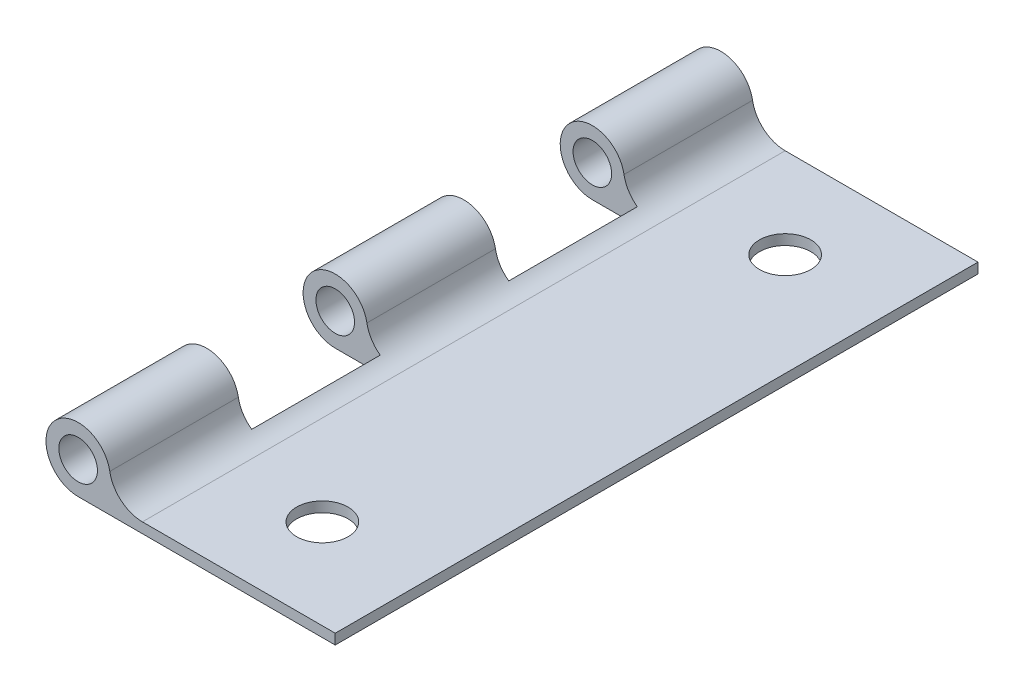
SolidWorks part; units mm, degrees
material "Aço cromo inoxidável"
ref_plane "Plano frontal" through (0, 0, 0) normal (0, 0, 1) x (1, 0, 0)
ref_plane "Plano superior" through (0, 0, 0) normal (0, 1, 0) x (1, 0, 0)
ref_plane "Plano direito" through (0, 0, 0) normal (1, 0, 0) x (0, 0, -1)
sketch "Esboço1" plane through (0, 0, 0) normal (0, 0, 1) x (1, 0, 0)
  line L0 (0, 0) -> (-20, 0)
  line L2 (-15, 0.8) -> (0, 0.8)
  line L3 (0, 0.8) -> (0, 0)
  arc A0 (-20, 0) -> (-19.9579, 4.9996) centre (-20, 2.5) cw
  arc A1 (-19.9579, 4.9996) -> (-17.5375, 2.9315) centre (-20, 2.5) cw
  arc A2 (-17.5375, 2.9315) -> (-15, 0.8) centre (-15, 3.3762) ccw
  circle A3 centre (-20, 2.5) radius 1.5
  circle A4 centre (-20, 2.5) radius 1.5 construction
  dimension "D4" = 20
  dimension "D5" = 1
  dimension "D1" = 0.8
  dimension "D3" = 5
extrude "Ressalto-extrusão1" add sketch "Esboço1" along normal blind 50
sketch "Esboço2" plane through (0, 0, 0) normal (0, -1, 0) x (1, 0, 0)
  line L0 (-22.5, 50) -> (-22.5, 0) construction
  line L1 (-22.5, 10) -> (-16.5, 10)
  line L2 (-22.5, 10) -> (-22.5, 20)
  line L3 (-22.5, 20) -> (-16.5, 20)
  line L4 (-16.5, 10) -> (-16.5, 20)
  line L5 (0, 50) -> (0, 0) construction
  line L6 (0, 50) -> (-15, 50) construction
  line L11 (-22.5, 30) -> (-22.5, 40)
  line L12 (-22.5, 30) -> (-16.5, 30)
  line L13 (-16.5, 30) -> (-16.5, 40)
  line L14 (-22.5, 40) -> (-16.5, 40)
  line L15 (-22.5, 0) -> (-17.5375, 0) construction
  line L16 (0, 25) -> (-6.2647, 25) construction
  line L17 (0, 50) -> (0, 0) construction
  line L18 (-22.5, 20) -> (-22.5, 30) [skipped]
  line L19 (-16.5, 20) -> (-16.5, 30) [skipped]
  line L20 (-22.5, 30) -> (-16.5, 30) [skipped]
  line L21 (-22.5, 20) -> (-16.5, 20) [skipped]
  circle A0 centre (-8, 43) radius 2
  circle A1 centre (-8, 7) radius 2
  dimension "D8" = 4
  dimension "D1" = 10
  dimension "D2" = 3
  dimension "D3" = 10
  dimension "D4" = 10
  dimension "D5" = 6
  dimension "D6" = 8
  dimension "D7" = 7
extrude "Corte-extrusão1" cut sketch "Esboço2" against normal through all
